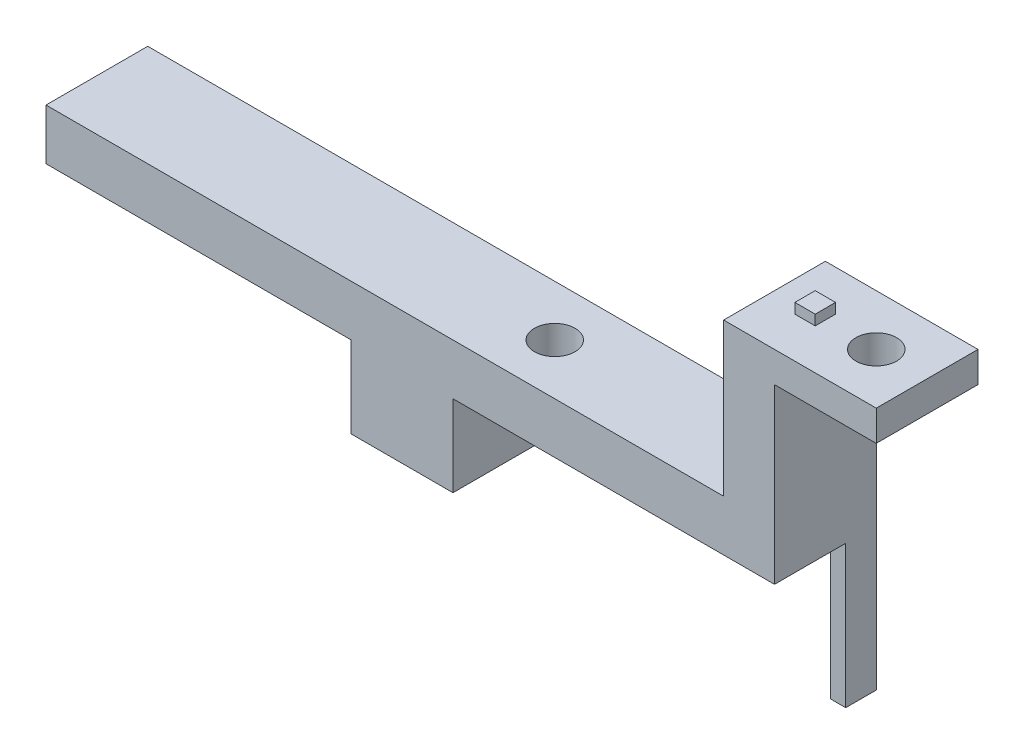
SolidWorks part; units mm, degrees
ref_plane "Front Plane" through (0, 0, 0) normal (0, 0, 1) x (1, 0, 0)
ref_plane "Top Plane" through (0, 0, 0) normal (0, 1, 0) x (1, 0, 0)
ref_plane "Right Plane" through (0, 0, 0) normal (1, 0, 0) x (0, 0, -1)
sketch "Sketch1" plane through (0, 0, 0) normal (0, 0, 1) x (1, 0, 0)
  line L0 (0, 8.6428) -> (0, -8.815) construction
  line L1 (-7.8399, 0) -> (7.1786, 0) construction
  line L2 (36.6, -2.7124) -> (36.6, 24.7717) construction
  line L3 (-5.2779, 28) -> (40.9314, 28) construction
  line L4 (10, 13) -> (36.6, 13)
  line L5 (0, 13) -> (10, 13)
  line L6 (0, 13) -> (0, 0)
  line L7 (0, 0) -> (10, 0)
  line L8 (10, 8) -> (10, 0)
  line L9 (36.6, 13) -> (36.6, 28)
  line L11 (41.6, 25) -> (41.6, 8)
  line L12 (41.6, 8) -> (10, 8)
  line L13 (41.6, 25) -> (51.6, 25)
  line L14 (51.6, 25) -> (51.6, 28)
  line L16 (36.6, 28) -> (51.6, 28)
  dimension "D4" = 15
  dimension "D1" = 36.6
  dimension "D2" = 10
  dimension "D3" = 13
  dimension "D5" = 15
  dimension "D6" = 5
  dimension "D7" = 5
  dimension "D8" = 3
  dimension "D9" = 8
  dimension "D10" = 31.6
extrude "Boss-Extrude1" add sketch "Sketch1" along normal blind 10
sketch "Sketch2" plane through (0, 0, 0) normal (0, -1, 0) x (1, 0, 0)
  line L0 (5, 15.6268) -> (5, -4.9051) construction
  line L1 (2.45, 6.55) -> (7.55, 6.55)
  line L2 (2.45, 6.55) -> (2.45, 3.45)
  line L3 (2.45, 3.45) -> (7.55, 3.45)
  line L4 (7.55, 6.55) -> (7.55, 3.45)
  line L5 (-4.1598, 5) -> (14.1324, 5) construction
  line L11 (0, 0) -> (10, 0) construction
  line L12 (0, 10) -> (0, 0) construction
  dimension "D1" = 5
  dimension "D2" = 5
  dimension "D3" = 5.1
  dimension "D4" = 3.1
extrude "Cut-Extrude1" cut sketch "Sketch2" against normal blind 10 contours L2 L1 L4 L3
sketch "Sketch3" plane through (0, 28, 0) normal (0, 1, 0) x (1, 0, 0)
  line L0 (29.4648, -5) -> (60.8247, -5) construction
  line L3 (51.6, 0) -> (36.6, 0) construction
  line L4 (51.6, -10) -> (51.6, 0) construction
  line L6 (39.6, -6) -> (41.6, -6)
  line L7 (39.6, -6) -> (39.6, -4)
  line L8 (39.6, -4) -> (41.6, -4)
  line L9 (41.6, -6) -> (41.6, -4)
  circle A0 centre (46.6, -5) radius 2
  dimension "D2" = 4
  dimension "D3" = 3
  dimension "D1" = 5
  dimension "D4" = 2
  dimension "D5" = 2
  dimension "D6" = 3
extrude "Boss-Extrude2" add sketch "Sketch3" along normal blind 1 contours L7 L6 L9 L8
sketch "Sketch11" plane through (0, 28, 0) normal (0, 1, 0) x (1, 0, 0)
  line L0 (29.4648, -5) -> (60.8247, -5) construction
  line L2 (51.6, -10) -> (51.6, 0) construction
  line L5 (39.6, -6) -> (41.6, -6) construction
  line L6 (39.6, -6) -> (41.6, -6)
  line L7 (39.6, -6) -> (39.6, -4)
  line L8 (39.6, -4) -> (41.6, -4)
  line L9 (41.6, -6) -> (41.6, -4)
  circle A0 centre (46.6, -5) radius 2
  dimension "D2" = 4
  dimension "D3" = 0
  dimension "D1" = 3
  dimension "D4" = 2
  dimension "D5" = 2
  dimension "D6" = 3
extrude "Cut-Extrude4" cut sketch "Sketch11" against normal up to next contours A0
sketch "Sketch12" plane through (0, 8, 0) normal (0, -1, 0) x (1, 0, 0)
  line L0 (10, 0) -> (41.6, 0) construction
  line L1 (41.6, 3) -> (40.1, 3)
  line L2 (41.6, 3) -> (41.6, 0)
  line L3 (41.6, 0) -> (40.1, 0)
  line L4 (40.1, 3) -> (40.1, 0)
  line L5 (41.6, 10) -> (41.6, 0) construction
  line L6 (60.8694, 4.3561) -> (126.3325, 4.3561)
  dimension "D1" = 1.5
  dimension "D2" = 3
extrude "Boss-Extrude4" add sketch "Sketch12" along normal blind 14 contours L1 L4 L0 L5 region at (40.85, 8, 1.5)
sketch "Sketch13" plane through (0, 13, 0) normal (0, 1, 0) x (1, 0, 0)
  line L6 (36.6, 0) -> (0, 0) construction
  line L7 (0, -10) -> (0, 0) construction
  circle A0 centre (15, -5) radius 2
  dimension "D1" = 4
  dimension "D2" = 5
  dimension "D3" = 15
extrude "Cut-Extrude6" cut sketch "Sketch13" against normal blind 3
sketch "Sketch14" plane through (0, 0, 0) normal (-1, 0, 0) x (0, 0, 1)
  line L0 (10, 13) -> (10, 0) construction
  line L1 (0, 13) -> (10, 13)
  line L2 (0, 13) -> (0, 8)
  line L3 (0, 8) -> (10, 8)
  line L4 (10, 13) -> (10, 8)
  dimension "D1" = 5
extrude "Boss-Extrude5" add sketch "Sketch14" along normal blind 30
